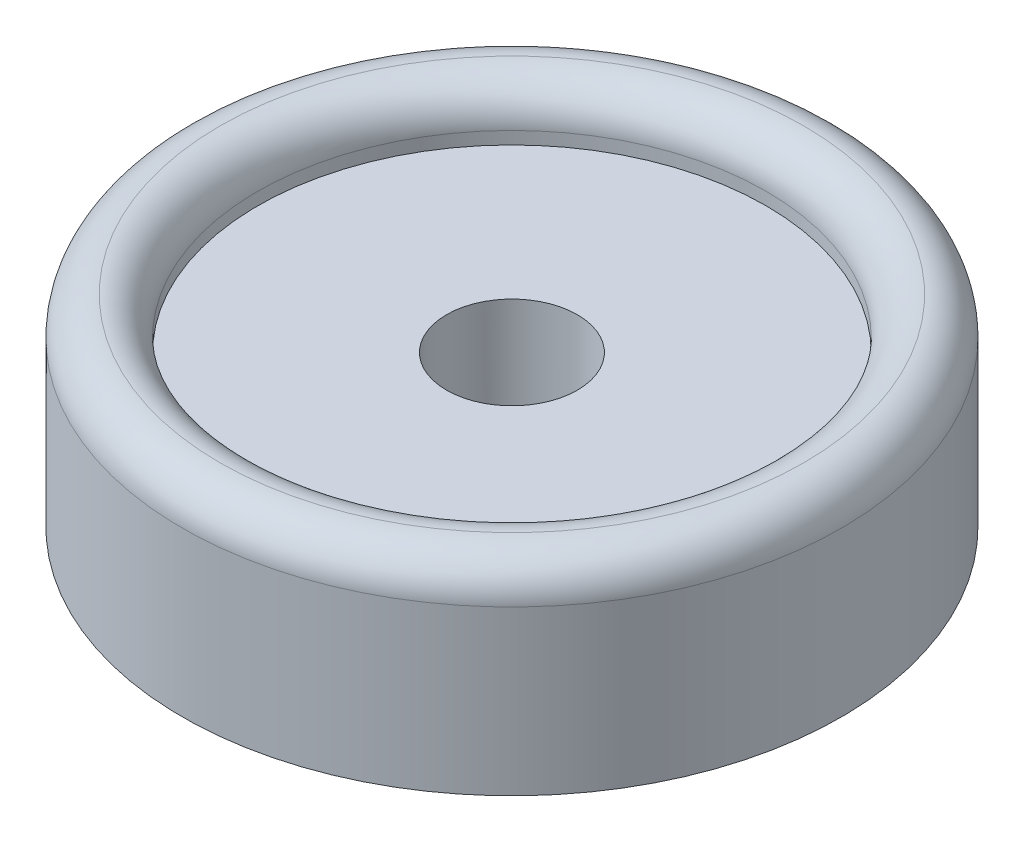
SolidWorks part; units mm, degrees
ref_plane "Front Plane" through (0, 0, 0) normal (0, 0, 1) x (1, 0, 0)
ref_plane "Top Plane" through (0, 0, 0) normal (0, 1, 0) x (1, 0, 0)
ref_plane "Right Plane" through (0, 0, 0) normal (1, 0, 0) x (0, 0, -1)
sketch "Sketch1" plane through (0, 0, 0) normal (0, 1, 0) x (1, 0, 0)
  circle A0 centre (0, 0) radius 7.1
  circle A1 centre (0, 0) radius 10.1
  dimension "D1" = 3
  dimension "D2" = 14.2
extrude "Boss-Extrude1" add sketch "Sketch1" along normal mid plane 100
sketch "Sketch2" plane through (0, -50, 0) normal (0, -1, 0) x (1, 0, 0)
  circle A0 centre (0, 0) radius 11.1
sketch "Sketch3" plane through (0, 0, 0) normal (0, 0, 1) x (1, 0, 0)
  line L1 (-101.5851, -102.8012) -> (101.5851, -102.8012)
  line L2 (-101.5851, -102.8012) -> (-101.5851, 102.8012)
  line L3 (-101.5851, 102.8012) -> (101.5851, 102.8012)
  line L4 (101.5851, -102.8012) -> (101.5851, 102.8012)
  line L5 (-101.5851, -102.8012) -> (101.5851, 102.8012) construction
  line L6 (-101.5851, 102.8012) -> (101.5851, -102.8012) construction
  point P0 (0, 0)
extrude "Cut-Extrude1" cut sketch "Sketch3" along normal through all
sketch "Sketch4" plane through (0, -50, 0) normal (0, -1, 0) x (1, 0, 0)
  circle A0 centre (0, 0) radius 10.1
  dimension "D1" = 20.2
extrude "Boss-Extrude3" add sketch "Sketch4" along normal blind 6
sketch "Sketch5" plane through (0, -50, 0) normal (0, 1, 0) x (1, 0, 0)
  circle A0 centre (0, 0) radius 2.6
  dimension "D1" = 5.2
extrude "Cut-Extrude2" cut sketch "Sketch5" against normal through all both and the other way through all
ref_plane "Plane2" through (0, 0, -6) normal (0, 0, 1) x (1, 0, 0)
sketch "Sketch6" plane through (0, 0, -6) normal (0, 0, 1) x (1, 0, 0)
  line L0 (0, 17.3633) -> (0, 69.1455) construction
  line L1 (10.1, 50) -> (7.1, 50) construction
  line L2 (7.6, 40) -> (22.6, 40)
  line L3 (7.6, 40) -> (7.6, 10)
  line L4 (7.6, 10) -> (22.6, 10)
  line L5 (22.6, 40) -> (22.6, 10)
  line L7 (-22.6, 40) -> (-22.6, 10)
  line L8 (-7.6, 10) -> (-22.6, 10)
  line L9 (-7.6, 40) -> (-7.6, 10)
  line L10 (-7.6, 40) -> (-22.6, 40)
  dimension "D1" = 10
  dimension "D2" = 30
  dimension "D3" = 7.6
  dimension "D4" = 15
extrude "Boss-Extrude4" add sketch "Sketch6" along normal mid plane 3
sketch "Sketch7" plane through (0, 0, -7.5) normal (0, 0, -1) x (-1, 0, 0)
  line L0 (15.1, 40) -> (15.1, 10) construction
  line L1 (7.6, 40) -> (22.6, 40) construction
  line L2 (22.6, 10) -> (7.6, 10) construction
  line L3 (0, 0) -> (0, 47.416) construction
  text T0 "A2N\r\n2mm mold" font "Century Gothic" height in points 11
extrude "Boss-Extrude5" add sketch "Sketch7" along normal blind 1.5
sketch "Sketch8" plane through (0, 0, -4.5) normal (0, 0, 1) x (1, 0, 0)
  line L1 (-37.752, -50) -> (43.0201, -50)
  line L2 (-37.752, -50) -> (-37.752, 64.2964)
  line L3 (-37.752, 64.2964) -> (43.0201, 64.2964)
  line L4 (43.0201, -50) -> (43.0201, 64.2964)
extrude "Cut-Extrude3" cut sketch "Sketch8" against normal through all both and the other way through all
sketch "Sketch9" plane through (0, -56, 0) normal (0, -1, 0) x (1, 0, 0)
  circle A0 centre (0, 0) radius 10.1
  circle A1 centre (0, 0) radius 13.1
  dimension "D1" = 3
extrude "Boss-Extrude6" add sketch "Sketch9" against normal blind 8
fillet "Fillet1" radius 1.5 2 edges at (0, -48, -13.1) (0, -48, -10.1)
